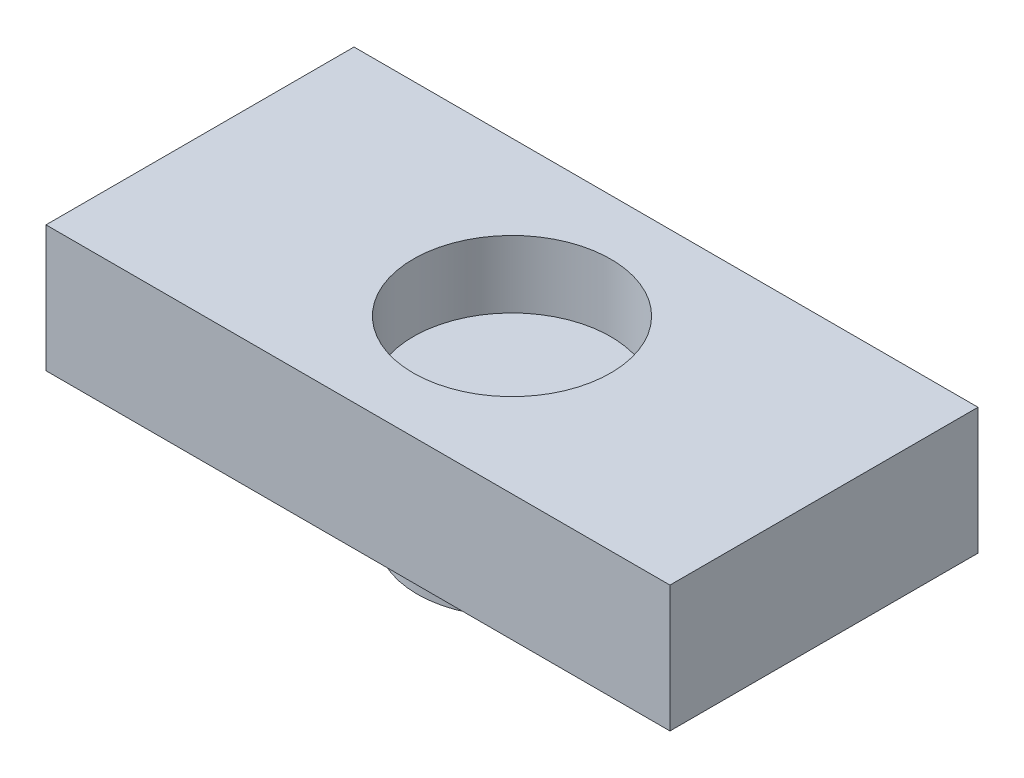
SolidWorks part; units mm, degrees
ref_plane "Спереди" through (0, 0, 0) normal (0, 0, 1) x (1, 0, 0)
ref_plane "Сверху" through (0, 0, 0) normal (0, 1, 0) x (1, 0, 0)
ref_plane "Справа" through (0, 0, 0) normal (1, 0, 0) x (0, 0, -1)
sketch "Эскиз1" plane through (0, 0, 0) normal (0, 1, 0) x (1, 0, 0)
  line L1 (7.9, -3.9) -> (-7.9, -3.9)
  line L2 (7.9, -3.9) -> (7.9, 3.9)
  line L3 (7.9, 3.9) -> (-7.9, 3.9)
  line L4 (-7.9, -3.9) -> (-7.9, 3.9)
  line L5 (7.9, -3.9) -> (-7.9, 3.9) construction
  line L6 (7.9, 3.9) -> (-7.9, -3.9) construction
  circle A0 centre (0, 0) radius 2.4
  point P0 (0, 0)
  dimension "D3" = 4.8
  dimension "D1" = 15.8
  dimension "D2" = 7.8
extrude "Бобышка-Вытянуть1" add sketch "Эскиз1" along normal blind 3.2 contours A0 | L4 L1 L2 L3 A0 | A0 | L2 L1 L4 L3 region at (0, 0, 3.7238) region at (0, 0, 0)
sketch "Эскиз2" plane through (0, 0, 0) normal (0, 1, 0) x (1, 0, 0)
  circle A0 centre (0, 0) radius 2.4
  circle A1 centre (0, 0) radius 1.6
  dimension "D1" = 4.8
  dimension "D2" = 3.2
extrude "Бобышка-Вытянуть2" add sketch "Эскиз2" against normal blind 1.7
sketch "Эскиз4" plane through (0, 3.2, 0) normal (0, 1, 0) x (1, 0, 0)
  circle A0 centre (0, 0) radius 2.5
extrude "Вырез-Вытянуть3" cut sketch "Эскиз4" against normal blind 1.7
